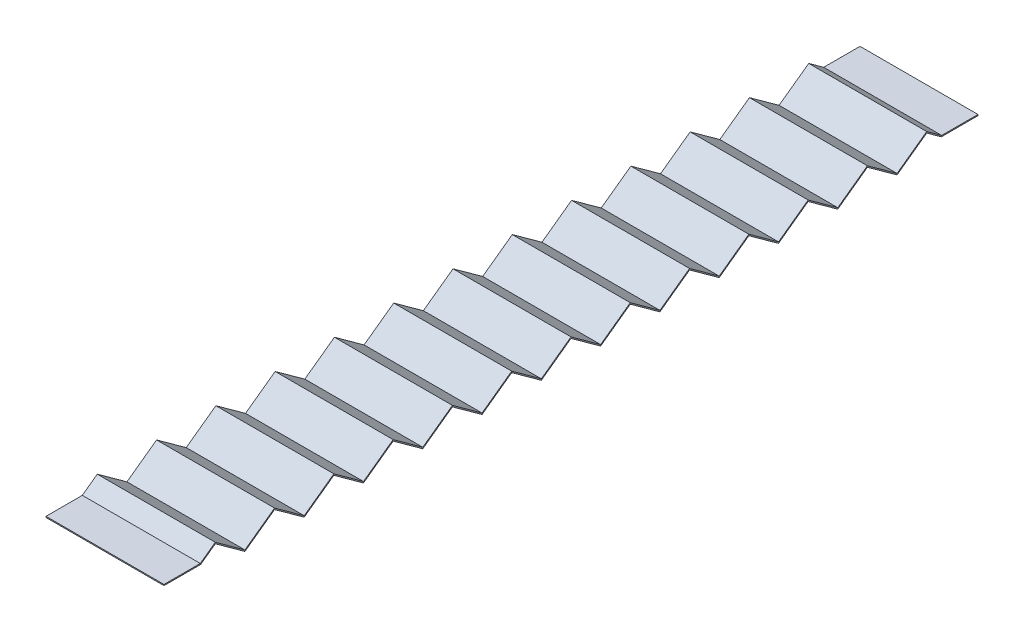
SolidWorks part; units mm, degrees
ref_plane "Front Plane" through (0, 0, 0) normal (0, 0, 1) x (1, 0, 0)
ref_plane "Top Plane" through (0, 0, 0) normal (0, 1, 0) x (1, 0, 0)
ref_plane "Right Plane" through (0, 0, 0) normal (1, 0, 0) x (0, 0, -1)
sketch "Sketch2" plane through (0, 0, 0) normal (0, 0, 1) x (1, 0, 0)
  line L1 (-27.5, 10) -> (27.5, 10)
  line L2 (-27.5, 10) -> (-27.5, 0)
  line L3 (-27.5, 0) -> (27.5, 0)
  line L4 (27.5, 10) -> (27.5, 0)
  point P4 (0, 0)
  dimension "D1" = 10
  dimension "D2" = 55
sketch "Sketch3" plane through (0, 0, 0) normal (1, 0, 0) x (0, 0, -1)
  line L0 (0, 10) -> (379.429, 10) construction
  line L1 (0, 0) -> (379.429, 0) construction
  line L2 (379.429, 4.75) -> (379.429, 22.75) construction
  line L3 (17, 5) -> (23.9086, 10)
  line L4 (23.9086, 10) -> (37.7257, 0)
  line L5 (37.7257, 0) -> (51.5429, 10)
  line L6 (51.5429, 10) -> (65.3601, 0)
  line L7 (65.3601, 0) -> (79.1772, 10)
  line L8 (79.1772, 10) -> (92.9944, 0)
  line L9 (92.9944, 0) -> (106.8115, 10)
  line L10 (106.8115, 10) -> (120.6287, 0)
  line L11 (120.6287, 0) -> (134.4459, 10)
  line L12 (134.4459, 10) -> (148.263, 0)
  line L13 (148.263, 0) -> (162.0802, 10)
  line L14 (162.0802, 10) -> (175.8974, 0)
  line L15 (175.8974, 0) -> (189.7145, 10)
  line L16 (189.7145, 10) -> (203.5317, 0)
  line L17 (203.5317, 0) -> (217.3488, 10)
  line L18 (217.3488, 10) -> (231.166, 0)
  line L19 (0, 10) -> (0, 0) construction
  line L20 (231.166, 0) -> (244.9832, 10)
  line L21 (244.9832, 10) -> (258.8003, 0)
  line L22 (258.8003, 0) -> (272.6175, 10)
  line L23 (272.6175, 10) -> (286.4346, 0)
  line L24 (286.4346, 0) -> (300.2518, 10)
  line L25 (300.2518, 10) -> (314.069, 0)
  line L26 (314.069, 0) -> (327.8861, 10)
  line L27 (327.8861, 10) -> (341.7033, 0)
  line L28 (341.7033, 0) -> (355.5204, 10)
  line L29 (355.5204, 10) -> (362.429, 5)
  line L30 (379.429, 10) -> (379.429, 0) construction
  line L31 (17, 5) -> (0, 5)
  line L32 (362.429, 5) -> (379.429, 5)
  dimension "D2" = 17
  dimension "D1" = 10
  dimension "D3" = 17
extrude "Extrude-Thin1" add sketch "Sketch3" against normal mid plane 55 thin thin type mid plane wall 0.5
